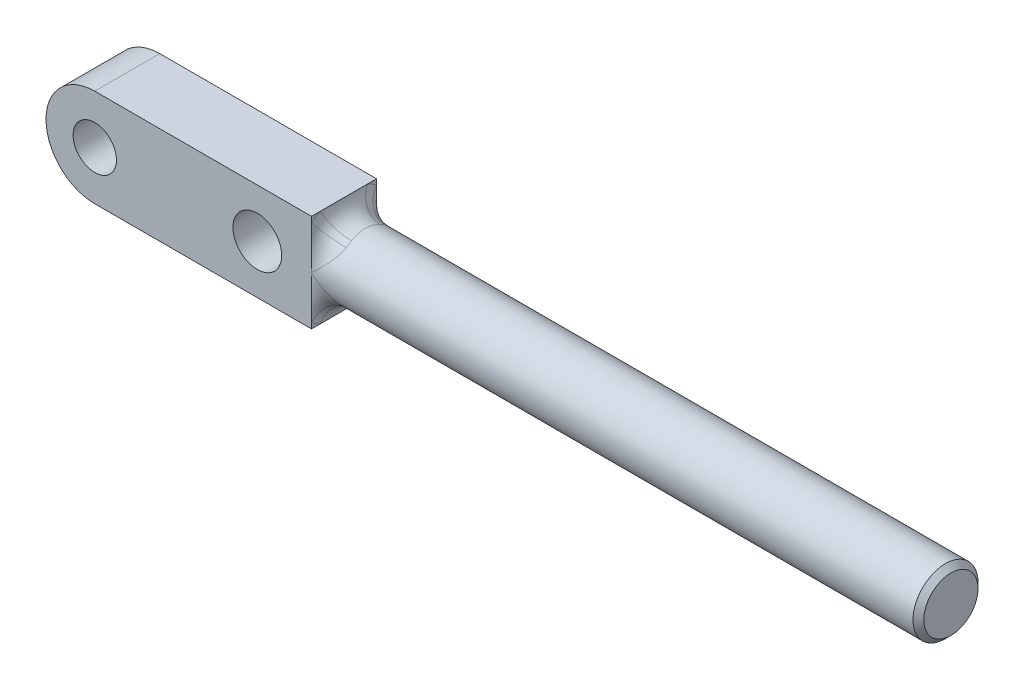
SolidWorks part; units mm, degrees
ref_plane "Front Plane" through (0, 0, 0) normal (0, 0, 1) x (1, 0, 0)
ref_plane "Top Plane" through (0, 0, 0) normal (0, 1, 0) x (1, 0, 0)
ref_plane "Right Plane" through (0, 0, 0) normal (1, 0, 0) x (0, 0, -1)
sketch "Sketch1" plane through (0, 0, 0) normal (0, 0, 1) x (1, 0, 0)
  line L1 (-2.6681, -4.5) -> (-22.6681, -4.5)
  line L2 (-2.6681, -4.5) -> (-2.6681, 4.5)
  line L3 (-2.6681, 4.5) -> (-22.6681, 4.5)
  arc A0 (-22.6681, 4.5) -> (-22.6681, -4.5) centre (-22.6681, 0) ccw
  circle A1 centre (-7.6681, 0) radius 2.25
  circle A2 centre (-22.6681, 0) radius 2
  point P0 (0, 0)
  dimension "D1" = 4.5
  dimension "D2" = 4
  dimension "D3" = 4.5
  dimension "D4" = 15
  dimension "D5" = 20
extrude "Boss-Extrude1" add sketch "Sketch1" along normal mid plane 6
sketch "Sketch2" plane through (-2.6681, 0, 0) normal (1, 0, 0) x (0, 0, -1)
  circle A0 centre (0, 0) radius 3
  dimension "D1" = 6
extrude "Boss-Extrude2" add sketch "Sketch2" along normal blind 56
fillet "Fillet1" radius 2 2 edges at (-2.6681, 3, 0) (-2.6681, -3, 0)
chamfer "Chamfer1" distance 0.5 angle 45 1 edges at (53.3319, 0, -3)
